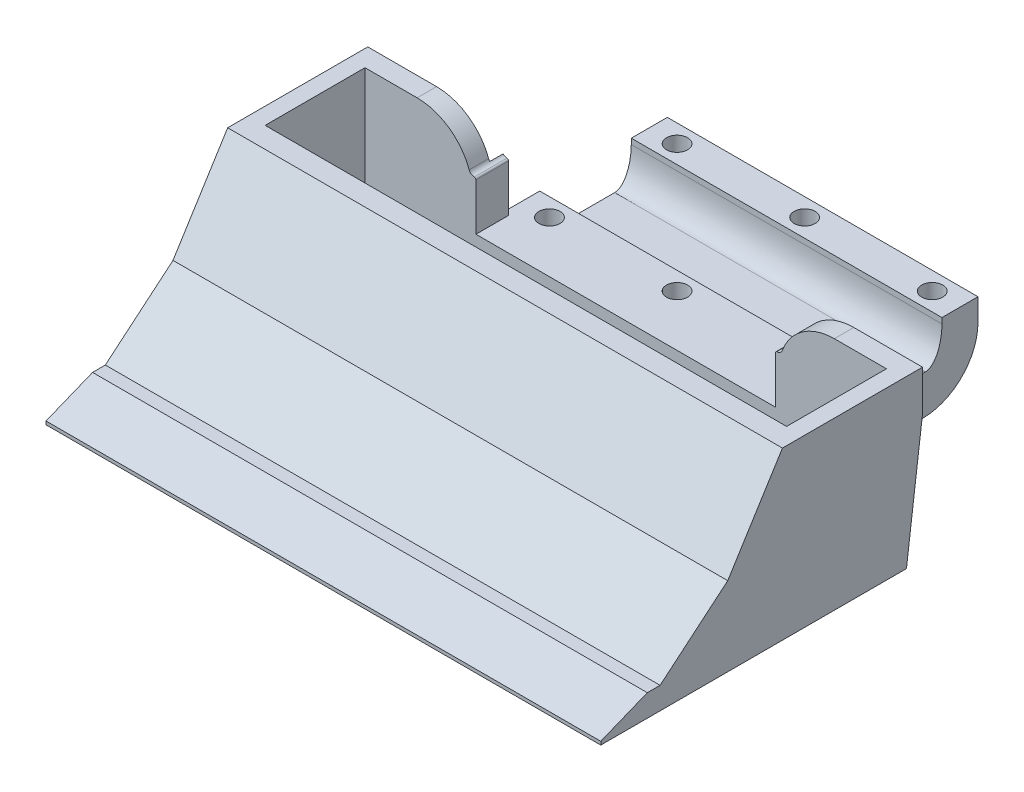
SolidWorks part; units mm, degrees
ref_plane "Plano frontal" through (0, 0, 0) normal (0, 0, 1) x (1, 0, 0)
ref_plane "Plano superior" through (0, 0, 0) normal (0, 1, 0) x (1, 0, 0)
ref_plane "Plano direito" through (0, 0, 0) normal (1, 0, 0) x (0, 0, -1)
sketch "Esboço2" plane through (0, 0, 0) normal (0, 1, 0) x (1, 0, 0)
  line L0 (0, 0) -> (0, 58)
  line L1 (0, 58) -> (22, 58)
  line L2 (22, 58) -> (22, 90)
  line L3 (22, 90) -> (78, 90)
  line L4 (78, 90) -> (78, 58)
  line L5 (78, 58) -> (100, 58)
  line L6 (100, 58) -> (100, 0)
  line L7 (100, 0) -> (0, 0)
  dimension "D1" = 100
  dimension "D2" = 56
  dimension "D3" = 90
  dimension "D5" = 32
extrude "Ressalto-extrusão1" add sketch "Esboço2" along normal blind 30
sketch "Esboço3" plane through (100, 0, 0) normal (1, 0, 0) x (0, 0, -1)
  line L0 (0, 0.6) -> (9.8284, 4.5709)
  line L1 (0, 30) -> (0, 0) construction
  line L2 (9.8284, 4.5709) -> (22.1268, 14.8905)
  line L3 (22.1268, 14.8905) -> (31.5683, 30)
  line L4 (0, 30) -> (58, 30) construction
  line L5 (31.5683, 30) -> (0, 30)
  line L6 (0, 30) -> (0, 0.6)
  line L7 (0, 0) -> (58, 0) construction
  dimension "D1" = 0.6
  dimension "D2" = 22
  dimension "D3" = 40
  dimension "D4" = 18
  dimension "D5" = 15.1095
  dimension "D6" = 12.2984
extrude "Corte-extrusão1" cut sketch "Esboço3" against normal blind 100
sketch "Esboço4" plane through (0, 0, 0) normal (0, -1, 0) x (1, 0, 0)
  line L0 (0, -58) -> (0, 0) construction
  line L1 (3, -53) -> (97, -53)
  line L2 (3, -53) -> (3, -28)
  line L3 (3, -28) -> (97, -28)
  line L4 (97, -53) -> (97, -28)
  line L5 (22, -58) -> (0, -58) construction
  dimension "D1" = 25
  dimension "D2" = 94
  dimension "D3" = 3
  dimension "D4" = 5
extrude "Corte-extrusão2" cut sketch "Esboço4" against normal blind 10
sketch "Esboço5" plane through (0, 30, 0) normal (0, 1, 0) x (1, 0, 0)
  line L0 (0, 58) -> (0, 31.5683) construction
  line L1 (3, 54.5) -> (97, 54.5)
  line L2 (3, 54.5) -> (3, 36.5)
  line L3 (3, 36.5) -> (97, 36.5)
  line L4 (97, 54.5) -> (97, 36.5)
  line L6 (100, 31.5683) -> (100, 58) construction
  line L7 (22, 58) -> (0, 58) construction
  dimension "D1" = 3
  dimension "D2" = 3
  dimension "D3" = 3.5
  dimension "D4" = 18
extrude "Corte-extrusão3" cut sketch "Esboço5" against normal blind 20 contours L2 L1 L4 L3
sketch "Esboço7" plane through (100, 0, 0) normal (1, 0, 0) x (0, 0, -1)
  line L0 (28, 10) -> (36.5, 30)
  line L1 (36.5, 30) -> (36.5, 10)
  line L2 (36.5, 10) -> (28, 10)
extrude "Corte-extrusão7" cut sketch "Esboço7" against normal up to surface (97 mm away) from surface up to face at (3, 12.5, -43) starting at face at (97, 12.5, -43)
sketch "Esboço8" plane through (78, 0, 0) normal (1, 0, 0) x (0, 0, -1)
  line L0 (90, 30) -> (90, 0) construction
  line L1 (58, 30) -> (90, 30)
  line L2 (58, 30) -> (58, 15)
  line L3 (58, 15) -> (90, 15)
  line L4 (90, 30) -> (90, 15)
  line L5 (58, 0) -> (90, 0) construction
  dimension "D1" = 15
extrude "Corte-extrusão8" cut sketch "Esboço8" against normal blind 56
sketch "Esboço9" plane through (78, 0, 0) normal (1, 0, 0) x (0, 0, -1)
  line L0 (67, 15) -> (67, 7)
  line L1 (58, 15) -> (90, 15) construction
  line L2 (67, 7) -> (83.5, 7)
  line L3 (83.5, 7) -> (83.5, 15)
  line L4 (83.5, 15) -> (67, 15)
  line L5 (90, 15) -> (90, 0) construction
  dimension "D1" = 16.5
  dimension "D2" = 8
  dimension "D3" = 6.5
extrude "Corte-extrusão9" cut sketch "Esboço9" against normal blind 56
fillet "Filete1" radius 6 1 edges at (50, 7, -67) second distance 3 first distance on face at (50, 11, -67)
fillet "Filete2" radius 3 1 edges at (50, 7, -83.5) second distance 6 first distance on face at (43, 7, -73.375)
fillet "Filete3" radius 10 1 edges at (50, 0, -90)
sketch "Esboço12" plane through (22, 0, 0) normal (-1, 0, 0) x (0, 0, 1)
  line L0 (-90, 15) -> (-58, 15)
  line L1 (-58, 15) -> (-58, 14)
  line L2 (-58, 15) -> (-58, 0) construction
  line L3 (-58, 14) -> (-90, 14)
  line L4 (-90, 15) -> (-90, 10) construction
  line L5 (-90, 14) -> (-90, 15)
  dimension "D1" = 1
extrude "Corte-extrusão12" cut sketch "Esboço12" against normal blind 68
sketch "Esboço14" plane through (0, 0, -58) normal (0, 0, -1) x (-1, 0, 0)
  line L0 (-78, 14) -> (-22, 14)
  line L1 (-22, 14) -> (-22, 30)
  line L2 (-100, 30) -> (0, 30) construction
  line L3 (-22, 30) -> (-78, 30)
  line L4 (-78, 30) -> (-78, 14)
extrude "Corte-extrusão13" cut sketch "Esboço14" against normal up to next
sketch "Esboço15" plane through (100, 0, 0) normal (1, 0, 0) x (0, 0, -1)
  line L12 (9.049, 4.256) -> (10.049, 4.256)
  line L13 (0, 0.6) -> (9.8284, 4.5709) construction
  line L14 (10.049, 4.256) -> (10.049, 4.756)
  line L15 (9.8284, 4.5709) -> (22.1268, 14.8905) construction
  line L16 (10.049, 4.756) -> (9.049, 4.256)
  dimension "D1" = 1
  dimension "D2" = 0.5
extrude "Corte-extrusão14" cut sketch "Esboço15" against normal through all
sketch "Esboço16" plane through (0, 14, 0) normal (0, 1, 0) x (1, 0, 0)
  line L0 (78, 90) -> (22, 90) construction
  line L1 (78, 90) -> (78, 83.5) construction
  line L2 (22, 90) -> (22, 83.5) construction
  line L3 (22, 75.25) -> (78, 75.25) construction
  line L4 (78, 70) -> (78, 80.5) construction
  line L5 (22, 70) -> (22, 80.5) construction
  line L6 (22, 90) -> (47, 90) construction
  line L7 (78, 90) -> (53, 90) construction
  circle A1 centre (73, 86.75) radius 1.9
  circle A2 centre (27, 86.75) radius 1.9
  circle A3 centre (73, 63.75) radius 1.9
  circle A5 centre (27, 63.75) radius 1.9
  circle A10 centre (50, 86.75) radius 1.9
  circle A11 centre (50, 63.75) radius 1.9
  point P11 (78, 86.75)
  point P16 (50, 90)
  dimension "D1" = 3.8
  dimension "D2" = 3.8
  dimension "D3" = 3.8
  dimension "D4" = 5
  dimension "D5" = 5
  dimension "D7" = 25
  dimension "D8" = 25
extrude "Corte-extrusão15" cut sketch "Esboço16" against normal through all
sketch "Esboço19" plane through (78, 0, 0) normal (-1, 0, 0) x (0, 0, 1)
  line L1 (-54.5, 14) -> (-60.39, 14)
  line L2 (-54.5, 14) -> (-54.5, 22.8)
  line L3 (-54.5, 22.8) -> (-60.39, 22.8)
  line L4 (-60.39, 14) -> (-60.39, 22.8)
extrude "Ressalto-extrusão4" add sketch "Esboço19" along normal blind 1
sketch "Esboço20" plane through (22, 0, 0) normal (1, 0, 0) x (0, 0, -1)
  line L1 (54.5, 14) -> (60.39, 14)
  line L2 (54.5, 14) -> (54.5, 22.8)
  line L3 (54.5, 22.8) -> (60.39, 22.8)
  line L4 (60.39, 14) -> (60.39, 22.8)
extrude "Ressalto-extrusão5" add sketch "Esboço20" along normal blind 1
fillet "Filete5" radius 10 2 edges at (22, 30, -56.25) (78, 30, -56.25)
fillet "Filete6" radius 0.3 2 edges at (77, 22.8, -57.445) (23, 22.8, -57.445)
fillet "Filete7" radius 1 2 edges at (22, 22.8, -56.25) (78, 22.8, -56.25)
sketch "Esboço22" plane through (0, 0, 0) normal (-1, 0, 0) x (0, 0, 1)
  line L5 (-58, 0) -> (-58, 22.7053)
  line L6 (-58, 23.1088) -> (-58, 0) construction
  line L7 (-58, 22.7053) -> (-55.1054, 0)
  line L8 (-58, 0) -> (0, 0) construction
  line L9 (-55.1054, 0) -> (-58, 0)
  dimension "D1" = 22.7053
  dimension "D2" = 277.265
extrude "Corte-extrusão17" cut sketch "Esboço22" against normal up to surface (22 mm away) up to face at (22, 11.5497, -72.4693)
sketch "Esboço23" plane through (100, 0, 0) normal (1, 0, 0) x (0, 0, -1)
  line L0 (58, 0) -> (55.1029, 0)
  line L1 (0, 0) -> (58, 0) construction
  line L2 (55.1029, 0) -> (58, 22.71)
  line L3 (58, 30) -> (58, 0) construction
  line L4 (58, 22.71) -> (58, 0)
  dimension "D1" = 22.71
  dimension "D2" = 277.27
extrude "Corte-extrusão18" cut sketch "Esboço23" against normal up to surface (22 mm away) up to face at (78, 11.5497, -72.9309)
sketch "Esboço27" plane through (0, 0, 0) normal (-1, 0, 0) x (0, 0, 1)
  line L0 (-31.5683, 30) -> (-22.1268, 14.8905)
  line L1 (-22.1268, 14.8905) -> (-10.049, 4.756)
  line L3 (-10.6918, 3.99) -> (-22.8909, 14.2263)
  line L4 (-22.8909, 14.2263) -> (-32.7474, 30)
  line L5 (-58, 30) -> (-31.5683, 30) construction
  line L6 (-32.7474, 30) -> (-31.5683, 30)
  line L7 (-10.6918, 3.99) -> (-7.995, 3.99)
  line L8 (-7.995, 3.99) -> (-10.049, 4.756)
  dimension "D1" = 1
  dimension "D2" = 1
extrude "Corte-extrusão19" cut sketch "Esboço27" against normal blind 124
